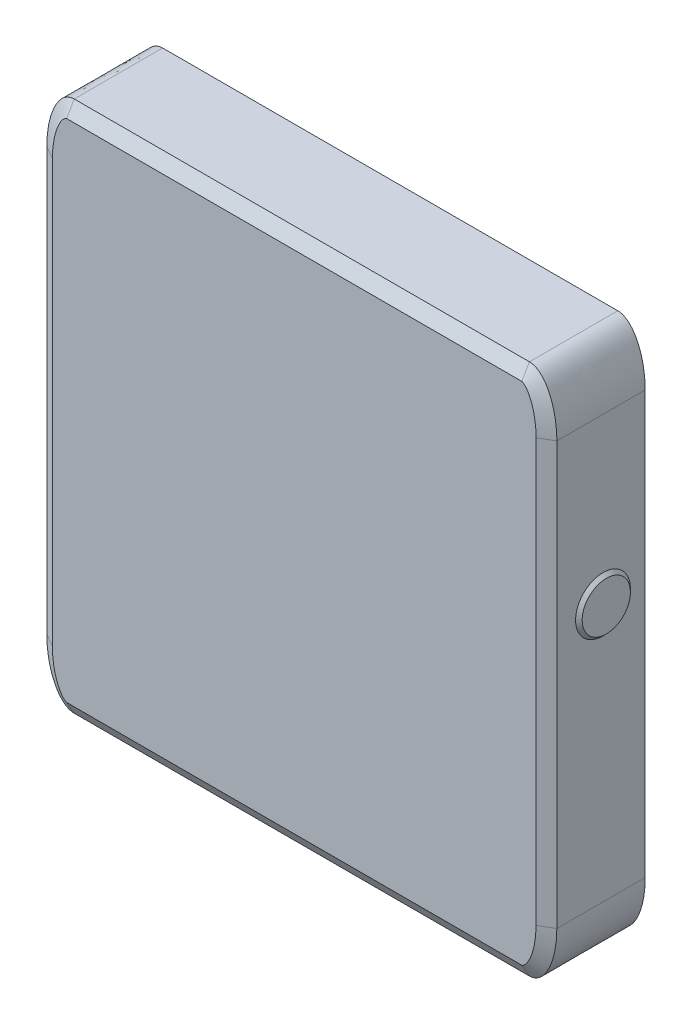
SolidWorks part; units mm, degrees
ref_plane "Front Plane" through (0, 0, 0) normal (0, 0, 1) x (1, 0, 0)
ref_plane "Top Plane" through (0, 0, 0) normal (0, 1, 0) x (1, 0, 0)
ref_plane "Right Plane" through (0, 0, 0) normal (1, 0, 0) x (0, 0, -1)
sketch "Sketch1" plane through (0, 0, 0) normal (0, 0, 1) x (1, 0, 0)
  line L1 (-46.5, 48.5) -> (46.5, 48.5)
  line L2 (-46.5, 48.5) -> (-46.5, -48.5)
  line L3 (-46.5, -48.5) -> (46.5, -48.5)
  line L4 (46.5, 48.5) -> (46.5, -48.5)
  line L5 (-46.5, 48.5) -> (46.5, -48.5) construction
  line L6 (-46.5, -48.5) -> (46.5, 48.5) construction
  point P0 (0, 0)
  dimension "D1" = 93
  dimension "D2" = 97
extrude "Boss-Extrude1" add sketch "Sketch1" along normal blind 17.5
fillet "Fillet1" radius 5 2 edges at (-46.5, 48.5, 8.75) (46.5, -48.5, 8.75) second distance 10 first distance on face at (0, 48.5, 8.75) first distance on face at (0, -48.5, 8.75)
fillet "Fillet2" radius 5 1 edges at (-46.5, -48.5, 8.75) second distance 10 first distance on face at (-24.5, -48.5, 6.5625)
fillet "Fillet3" radius 5 1 edges at (46.5, 48.5, 8.75) second distance 10 first distance on face at (24.5, 48.5, 6.5625)
sketch "Sketch2" plane through (0, -48.5, 0) normal (0, -1, 0) x (1, 0, 0)
  line L5 (-3.67, 10.03) -> (3.67, 10.03)
  line L6 (-3.67, 10.03) -> (-3.67, 7.47)
  line L7 (41.5, 0) -> (41.5, 17.5) construction
  line L8 (41.5, 8.75) -> (0, 8.75) construction
  line L9 (-3.67, 7.47) -> (3.67, 7.47)
  line L10 (3.67, 10.03) -> (3.67, 7.47)
  line L11 (-3.67, 10.03) -> (3.67, 7.47) construction
  line L12 (-3.67, 7.47) -> (3.67, 10.03) construction
  circle A0 centre (-3.67, 8.75) radius 1.28
  circle A1 centre (3.67, 8.75) radius 1.28
  dimension "D1" = 7.34
  dimension "D2" = 2.56
extrude "Cut-Extrude1" cut sketch "Sketch2" against normal blind 11.3 contours A0 | L6 L5 L10 L9 | A1
sketch "Sketch3" plane through (46.5, 0, 0) normal (1, 0, 0) x (0, 0, -1)
  line L0 (-17.5, 48.5) -> (0, 48.5) construction
  line L5 (-17.5, 48.5) -> (0, 48.5)
  line L6 (0, -38.5) -> (0, 38.5) construction
  circle A2 centre (-7.7, 8.5) radius 3.5 construction
  circle A3 centre (-7.7, 8.5) radius 5
  dimension "D1" = 7
  dimension "D3" = 7.7
  dimension "D4" = 10
  dimension "D2" = 40
extrude "Boss-Extrude2" add sketch "Sketch3" along normal blind 0.6 contours A3
chamfer "Chamfer1" distance 0.6 angle 45 1 edges at (47.1, 13.5, 7.7)
sketch "Sketch4" plane through (-46.5, 0, 0) normal (-1, 0, 0) x (0, 0, 1)
  line L0 (0, -51.5075) -> (0, 51.5075) construction
  line L1 (3, 34.5) -> (13.7, 34.5)
  line L2 (2, 33.5) -> (2, 6.8)
  line L3 (3, 5.8) -> (13.7, 5.8)
  line L4 (14.7, 33.5) -> (14.7, 6.8)
  line L5 (2, 34.5) -> (14.7, 5.8) construction
  line L6 (2, 5.8) -> (14.7, 34.5) construction
  line L7 (0, 48.5) -> (17.5, 48.5) construction
  line L8 (0, 48.5) -> (17.5, 48.5)
  arc A0 (13.7, 34.5) -> (14.7, 33.5) centre (13.7, 33.5) cw
  arc A1 (3, 34.5) -> (2, 33.5) centre (3, 33.5) ccw
  arc A2 (2, 6.8) -> (3, 5.8) centre (3, 6.8) ccw
  arc A3 (13.7, 5.8) -> (14.7, 6.8) centre (13.7, 6.8) ccw
  point P0 (8.35, 20.15)
  dimension "D5" = 1
  dimension "D1" = 2
  dimension "D2" = 14
  dimension "D3" = 28.7
  dimension "D4" = 12.7
extrude "Cut-Extrude2" cut sketch "Sketch4" against normal blind 0.2 contours L4 A3 L3 A2 L2 A1 L1 A0
chamfer "Chamfer4" distance 2.4 angle 30 8 edges first distance on face at (0, 0, 17.5)
sketch "Sketch5" plane through (0, 0, 0) normal (0, 0, -1) x (-1, 0, 0)
  line L0 (-41.5, 48.5) -> (41.5, 48.5) construction
  circle A0 centre (0, 29.5) radius 2
  point P4 (2.0336, 29)
  point P5 (0, 29)
  dimension "D1" = 19
  dimension "D2" = 4
extrude "Cut-Extrude3" cut sketch "Sketch5" against normal blind 5 contours A0
equation "\"DisplayHeight\"= 18mm"
equation "\"DisplayWidth\"= 93mm"
equation "\"DisplayTall\"= 97mm"
